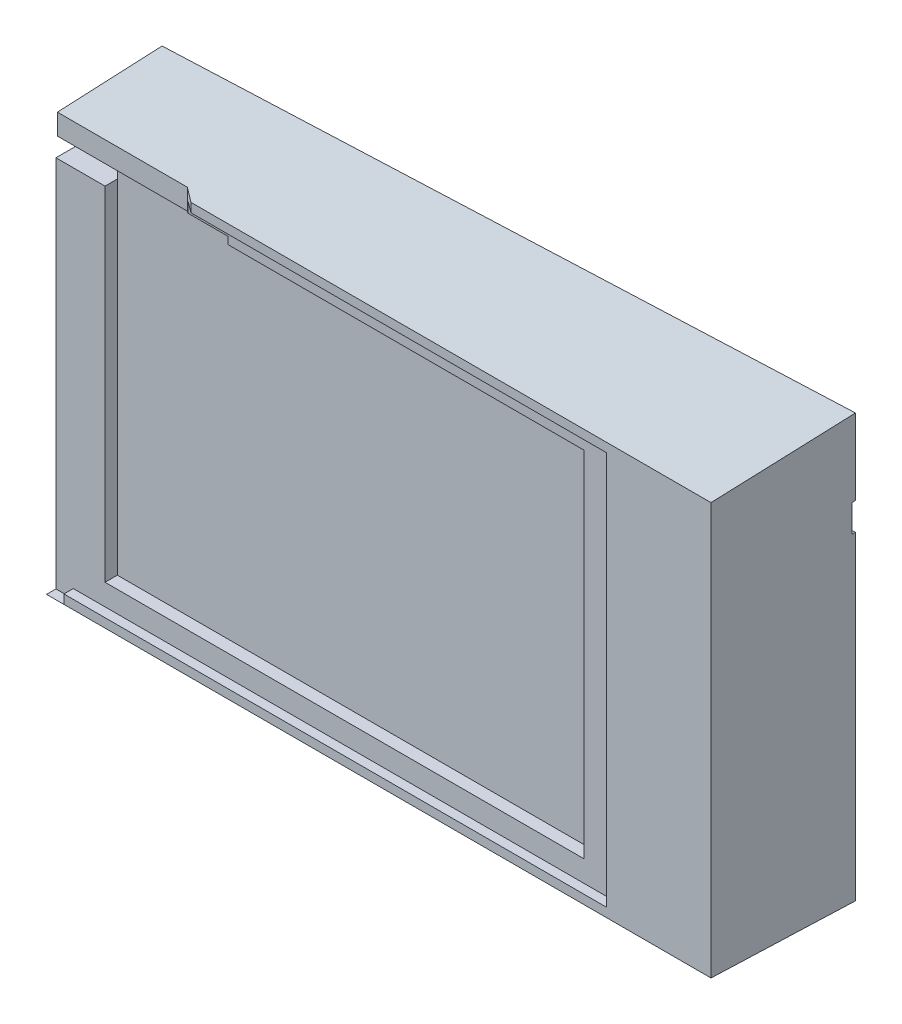
SolidWorks part; units mm, degrees
ref_plane "Front Plane" through (0, 0, 0) normal (0, 0, 1) x (1, 0, 0)
ref_plane "Top Plane" through (0, 0, 0) normal (0, 1, 0) x (1, 0, 0)
ref_plane "Right Plane" through (0, 0, 0) normal (1, 0, 0) x (0, 0, -1)
sketch "Sketch1" plane through (0, 0, 0) normal (0, 0, 1) x (1, 0, 0)
  line L1 (0, 0) -> (92, 0)
  line L2 (0, 0) -> (0, 61)
  line L3 (0, 61) -> (92, 61)
  line L4 (92, 0) -> (92, 61)
  dimension "D1" = 61
  dimension "D2" = 92
ref_plane "Plane1" through (92, 0, 0) normal (1, 0, 0) x (0, 0, -1)
sketch "Sketch2" plane through (92, 0, 0) normal (1, 0, 0) x (0, 0, -1)
  line L1 (0, 61) -> (20, 61.75)
  line L2 (0, 61) -> (0, 4)
  line L3 (0, 4) -> (20, 3.25)
  line L4 (20, 61.75) -> (20, 3.25)
  dimension "D1" = 20
  dimension "D2" = 57
  dimension "D3" = 58.5
ref_plane "Plane2" through (0, 0, 0) normal (1, 0, 0) x (0, 0, -1)
sketch "Sketch3" plane through (0, 0, 0) normal (1, 0, 0) x (0, 0, -1)
  line L1 (0, 61) -> (16, 61.75)
  line L2 (0, 61) -> (0, 4)
  line L3 (0, 4) -> (16, 3.25)
  line L4 (16, 61.75) -> (16, 3.25)
  point P5 (16, 1.6945)
  point P6 (16, 61)
  dimension "D1" = 16
  dimension "D2" = 58.5
  dimension "D3" = 57
ref_plane "Plane3" through (0, 61, 0) normal (0, 1, 0) x (1, 0, 0)
loft "body" add profiles "Sketch3", "Sketch2" connector at (0, 61.75, -16) connector at (92, 61.75, -20)
sketch "Sketch5" plane through (0, 61, 0) normal (0, 1, 0) x (1, 0, 0)
  line L0 (0, 1.5) -> (18, 1.5)
  line L1 (0, -33.55) -> (0, 33.55) construction
  line L2 (18, 1.5) -> (20, 0)
  line L3 (0, 0) -> (92, 0) construction
  line L4 (0, 1.5) -> (0, 0)
  line L5 (0, 0) -> (20, 0)
  dimension "D1" = 1.5
  dimension "D2" = 20
  dimension "D3" = 2
sketch "Sketch6" plane through (0, 0, 0) normal (0, 0, 1) x (1, 0, 0)
  line L0 (23.8, 57.2) -> (23.8, 58.2)
  line L1 (6.8, 8.2) -> (73.1, 8.2)
  line L2 (6.8, 8.2) -> (6.8, 57.2)
  line L3 (6.8, 57.2) -> (73.1, 57.2)
  line L4 (73.1, 8.2) -> (73.1, 57.2)
  line L5 (6.8, 8.2) -> (73.1, 57.2) construction
  line L6 (6.8, 57.2) -> (73.1, 8.2) construction
  line L7 (23.8, 58.2) -> (6.8, 58.2)
  line L9 (0, 61) -> (92, 61) construction
  line L10 (0, 0) -> (0, 61) construction
  line L11 (6.8, 57.2) -> (6.8, 58.2)
  line L12 (6.8, 58.2) -> (6.8, 57.2)
  point P0 (39.95, 32.7)
  dimension "D1" = 66.3
  dimension "D2" = 49
  dimension "D3" = 1
  dimension "D4" = 17
  dimension "D5" = 3.8
  dimension "D6" = 6.8
extrude "film plane" cut sketch "Sketch6" against normal blind 3 contours L11 L3 L0 L7 | L1 L4 L3 L2 region at (15.3, 57.7, 0) region at (39.95, 32.7, 0)
sketch "Sketch7" plane through (0, 0, 0) normal (0, 0, 1) x (1, 0, 0)
  line L0 (0, 0) -> (0, 61) construction
  line L1 (77.5, 59.75) -> (0, 59.75)
  line L2 (77.5, 59.75) -> (77.5, 5.25)
  line L3 (77.5, 5.25) -> (0, 5.25)
  line L4 (0, 59.75) -> (0, 5.25)
  line L5 (92, 0) -> (92, 61) construction
  line L6 (77.5, 5.25) -> (77.5, 4) construction
  line L7 (0, 4) -> (92, 4) construction
  line L8 (77.5, 59.75) -> (77.5, 61) construction
  line L9 (0, 61) -> (92, 61) construction
  line L10 (2.4, 5.25) -> (2.4, 4)
  line L11 (2.4, 4) -> (0, 4)
  line L12 (0, 4) -> (0, 5.25)
  line M5 (0, 4) -> (92, 4)
  dimension "D1" = 54.5
  dimension "D2" = 14.5
  dimension "D3" = 2.4
extrude "Cut-Extrude2" cut sketch "Sketch7" against normal blind 1.3 contours L10 L3 M5 | L3 L2 L1 L4 region at (1.2, 4.625, 0)
sketch "notch" plane through (0, 0, -1.3) normal (0, 0, 1) x (1, 0, 0)
  line L0 (6.8, 58.2) -> (0, 58.2)
  line L1 (0, 59.75) -> (0, 4) construction
  line L2 (0, 58.2) -> (0, 55.7)
  line L3 (0, 55.7) -> (6.8, 55.7)
  line L4 (6.8, 58.2) -> (6.8, 8.2) construction
  line L5 (6.8, 55.7) -> (6.8, 58.2)
  dimension "D1" = 2.5
extrude "notch-cut" cut sketch "notch" against normal blind 4.1
sketch "Sketch10" plane through (-0.6943, 0, -15.9698) normal (-0.0434, 0, -0.9991) x (-0.9991, 0, 0.0434)
  line L0 (-92.7819, 51.25) -> (-86.4841, 51.25)
  line L1 (-92.7819, 3.25) -> (-92.7819, 61.75) construction
  line L2 (-86.4841, 51.25) -> (-86.4841, 47.45)
  line L3 (-86.4841, 47.45) -> (-92.7819, 47.45)
  line L4 (-92.7819, 47.45) -> (-92.7819, 51.25)
  line L6 (-92.7819, 61.75) -> (-0.695, 61.75) construction
  dimension "D1" = 10.5
  dimension "D2" = 3.8
extrude "Cut-Extrude4" cut sketch "Sketch10" against normal blind 0.5
sketch "Sketch11" plane through (-0.6943, 0, -15.9698) normal (-0.0434, 0, -0.9991) x (-0.9991, 0, 0.0434)
  line L0 (-92.7819, 3.25) -> (-92.7819, 47.45) construction
  line L1 (-72.5, 14.5) -> (-64, 14.5)
  line L2 (-75, 17) -> (-75, 48)
  line L3 (-72.5, 50.5) -> (-64, 50.5)
  line L4 (-61.5, 17) -> (-61.5, 48)
  line L5 (-24.5, 14.5) -> (-16, 14.5)
  line L6 (-27, 17) -> (-27, 48)
  line L7 (-24.5, 50.5) -> (-16, 50.5)
  line L8 (-13.5, 17) -> (-13.5, 48)
  line L11 (-0.695, 32.5) -> (-92.7819, 32.5) construction
  line L12 (-0.695, 3.25) -> (-0.695, 61.75) construction
  line L13 (0, 0) -> (0, 61) construction
  arc A0 (-24.5, 14.5) -> (-27, 17) centre (-24.5, 17) cw
  arc A1 (-16, 14.5) -> (-13.5, 17) centre (-16, 17) ccw
  arc A2 (-16, 50.5) -> (-13.5, 48) centre (-16, 48) cw
  arc A3 (-27, 48) -> (-24.5, 50.5) centre (-24.5, 48) cw
  arc A4 (-75, 48) -> (-72.5, 50.5) centre (-72.5, 48) cw
  arc A5 (-64, 50.5) -> (-61.5, 48) centre (-64, 48) cw
  arc A6 (-64, 14.5) -> (-61.5, 17) centre (-64, 17) ccw
  arc A7 (-72.5, 14.5) -> (-75, 17) centre (-72.5, 17) cw
  point P10 (-13.5, 32.5)
  point P27 (-75, 50.5)
  point P34 (-75, 14.5)
  dimension "D6" = 2.5
  dimension "D1" = 36
  dimension "D3" = 34.5
  dimension "D4" = 13.5
  dimension "D2" = 13.5
  dimension "D5" = 13.5
extrude "Cut-Extrude5" cut sketch "Sketch11" against normal blind 1.5
extrude "Cut-Extrude6" cut sketch "Sketch5" against normal blind 5 and the other way through all
equation "\"D5@Sketch11\"=\"D2@Sketch11\""
